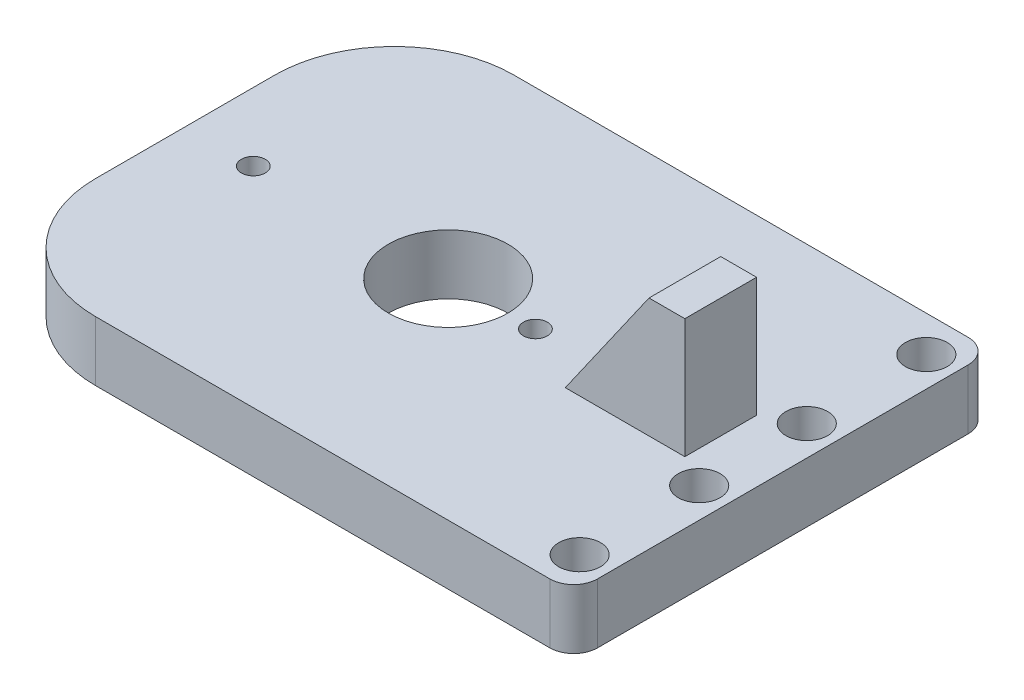
SolidWorks part; units mm, degrees
ref_plane "Front Plane" through (0, 0, 0) normal (0, 0, 1) x (1, 0, 0)
ref_plane "Top Plane" through (0, 0, 0) normal (0, 1, 0) x (1, 0, 0)
ref_plane "Right Plane" through (0, 0, 0) normal (1, 0, 0) x (0, 0, -1)
sketch "Sketch1" plane through (0, 0, 0) normal (0, 1, 0) x (1, 0, 0)
  line L1 (0, 0) -> (50, 0)
  line L2 (0, 0) -> (0, 35)
  line L3 (0, 35) -> (50, 35)
  line L4 (50, 0) -> (50, 35)
  circle A0 centre (22, 17.5) radius 5
  circle A1 centre (47.5, 32) radius 1.75
  circle A2 centre (47.5, 22) radius 1.75
  circle A3 centre (47.5, 13) radius 1.75
  circle A4 centre (47.5, 3) radius 1.75
  point P7 (0, 17.5)
  dimension "D4" = 10
  dimension "D5" = 3.5
  dimension "D1" = 35
  dimension "D2" = 50
  dimension "D3" = 28
  dimension "D6" = 2.5
  dimension "D7" = 10
  dimension "D8" = 3
  dimension "D9" = 10
  dimension "D10" = 3
extrude "Boss-Extrude1" add sketch "Sketch1" along normal blind 5 contours A0 | A1 | A2 | A3 | A4 | L2 L3 L4 L1 region at (22, 0, -17.5) region at (47.5, 0, -32) region at (47.5, 0, -22) region at (47.5, 0, -13) region at (47.5, 0, -3)
fillet "Fillet1" radius 10 2 edges at (0, 2.5, 0) (0, 2.5, -35)
fillet "Fillet2" radius 2 2 edges at (50, 2.5, 0) (50, 2.5, -35)
sketch "Sketch2" plane through (0, 5, 0) normal (0, 1, 0) x (1, 0, 0)
  line L0 (50, 2) -> (50, 33) construction
  line L1 (44.8, 20.5) -> (34.8, 20.5)
  line L2 (44.8, 20.5) -> (44.8, 14.5)
  line L3 (44.8, 14.5) -> (34.8, 14.5)
  line L4 (34.8, 20.5) -> (34.8, 14.5)
  point P4 (50, 17.5)
  point P5 (44.8, 17.5)
  dimension "D1" = 10
  dimension "D2" = 6
  dimension "D3" = 5.2
extrude "Boss-Extrude2" add sketch "Sketch2" along normal blind 10
chamfer "Chamfer1" distance 10 angle 35 1 edges at (34.8, 15, -17.5) first distance on face at (34.8, 10, -17.5)
sketch "Sketch3" plane through (0, 5, 0) normal (0, 1, 0) x (1, 0, 0)
  line L0 (50, 2) -> (50, 33) construction
  circle A0 centre (5.7, 17.5) radius 1
  circle A2 centre (29.3, 17.5) radius 1
  circle A3 centre (22, 17.5) radius 5 construction
  point P4 (50, 17.5)
  point P5 (0, 0)
  dimension "D1" = 2
  dimension "D2" = 16.3
  dimension "D3" = 7.3
extrude "Cut-Extrude1" cut sketch "Sketch3" against normal through all
